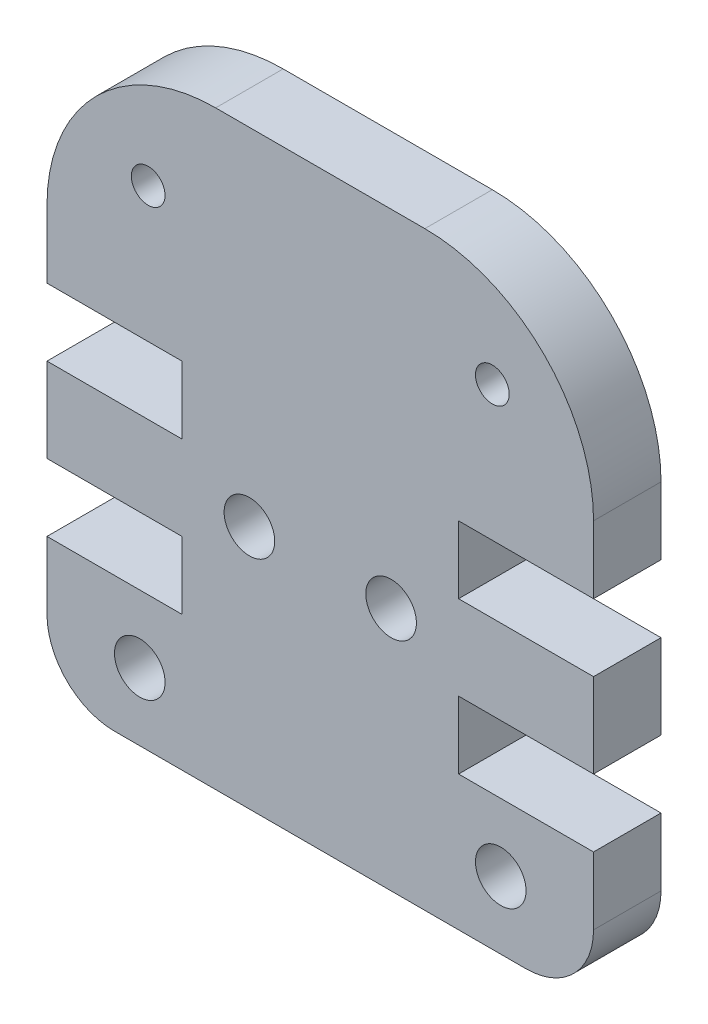
SolidWorks part; units mm, degrees
ref_plane "Front Plane" through (0, 0, 0) normal (0, 0, 1) x (1, 0, 0)
ref_plane "Top Plane" through (0, 0, 0) normal (0, 1, 0) x (1, 0, 0)
ref_plane "Right Plane" through (0, 0, 0) normal (1, 0, 0) x (0, 0, -1)
sketch "Sketch1" plane through (0, 0, 0) normal (0, 0, 1) x (1, 0, 0)
  line L12 (0, 12.5) -> (0, 10.5)
  line L13 (4, 10.5) -> (4, 8.5)
  line L14 (0, 8.5) -> (0, 6)
  line L15 (5, 17.5) -> (11.2, 17.5)
  line L16 (2, 0) -> (14.2, 0)
  line L17 (16.2, 2) -> (16.2, 4)
  line L18 (0, 2) -> (0, 4)
  line L19 (0, 6) -> (4, 6)
  line L20 (12.2, 4) -> (16.2, 4)
  line L21 (4, 6) -> (4, 4)
  line L22 (4, 4) -> (0, 4)
  line L23 (12.2, 6) -> (12.2, 4)
  line L24 (16.2, 6) -> (12.2, 6)
  line L25 (0, 10.5) -> (4, 10.5)
  line L26 (4, 8.5) -> (0, 8.5)
  line L27 (12.2, 8.5) -> (16.2, 8.5)
  line L28 (16.2, 10.5) -> (12.2, 10.5)
  line L29 (16.2, 8.5) -> (16.2, 6)
  line L30 (12.2, 10.5) -> (12.2, 8.5)
  line L31 (16.2, 12.5) -> (16.2, 10.5)
  circle A10 centre (10.2, 7.25) radius 0.75
  circle A11 centre (6, 7.25) radius 0.75
  arc A12 (14.2, 0) -> (16.2, 2) centre (14.2, 2) ccw
  arc A13 (5, 17.5) -> (0, 12.5) centre (5, 12.5) ccw
  arc A14 (16.2, 12.5) -> (11.2, 17.5) centre (11.2, 12.5) ccw
  circle A15 centre (3, 14.5) radius 0.5
  circle A16 centre (13.2, 14.5) radius 0.5
  arc A17 (0, 2) -> (2, 0) centre (2, 2) ccw
  circle A18 centre (13.45, 2) radius 0.75
  circle A19 centre (2.75, 2) radius 0.75
extrude "Boss-Extrude1" add sketch "Sketch1" along normal blind 2
